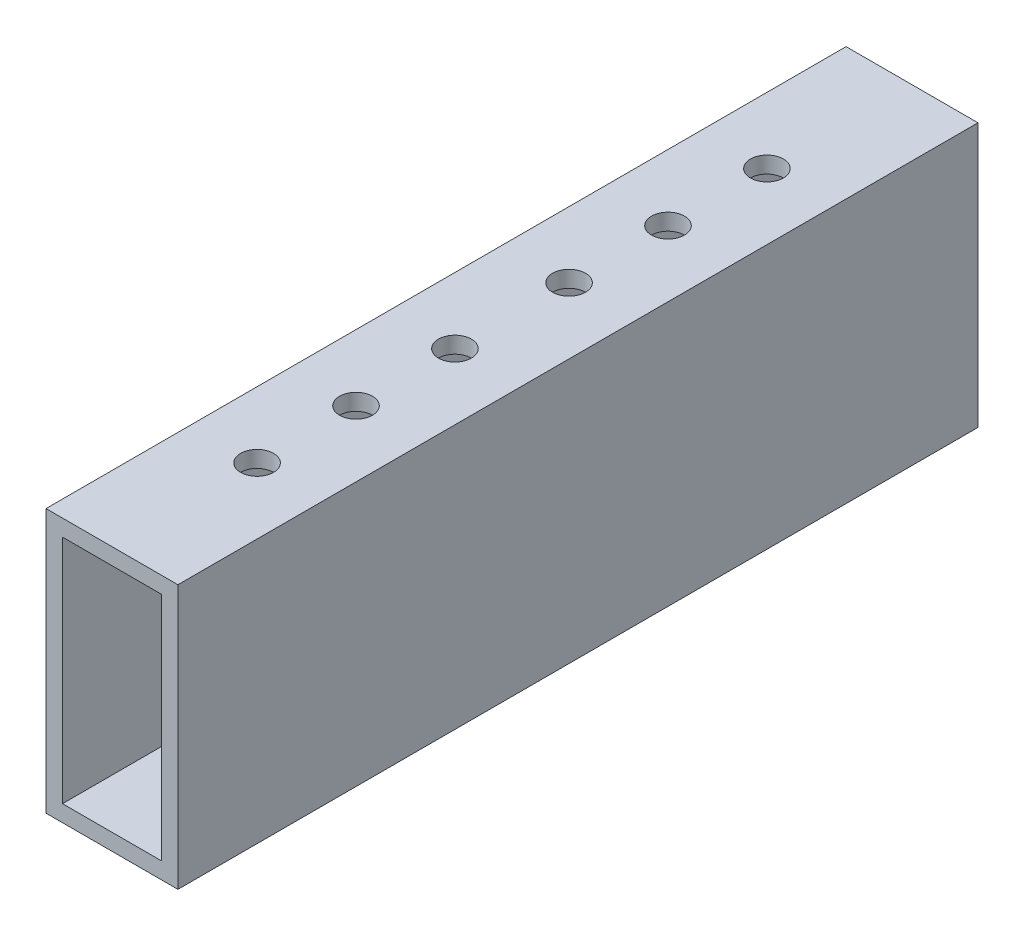
SolidWorks part; units mm, degrees
ref_plane "Front Plane" through (0, 0, 0) normal (0, 0, 1) x (1, 0, 0)
ref_plane "Top Plane" through (0, 0, 0) normal (0, 1, 0) x (1, 0, 0)
ref_plane "Right Plane" through (0, 0, 0) normal (1, 0, 0) x (0, 0, -1)
sketch "Sketch1" plane through (0, 0, 0) normal (0, 0, 1) x (1, 0, 0)
  line L0 (3.175, 47.625) -> (22.225, 47.625)
  line L1 (0, 0) -> (25.4, 0)
  line L2 (0, 0) -> (0, 50.8)
  line L3 (0, 50.8) -> (25.4, 50.8)
  line L4 (25.4, 0) -> (25.4, 50.8)
  line L5 (22.225, 3.175) -> (22.225, 47.625)
  line L6 (3.175, 3.175) -> (22.225, 3.175)
  line L7 (3.175, 3.175) -> (3.175, 47.625)
  dimension "D1" = 50.8
  dimension "D2" = 25.4
  dimension "D3" = 3.175
extrude "Boss-Extrude1" add sketch "Sketch1" along normal blind 154.051
sketch "Sketch2" plane through (0, 50.8, 0) normal (0, 1, 0) x (1, 0, 0)
  line L0 (25.4, -154.051) -> (0, -154.051) construction
  line L1 (0, -154.051) -> (0, 0) construction
  line L3 (0, -77.0255) -> (25.4, -77.0255) construction
  line L4 (25.4, -154.051) -> (25.4, 0) construction
  circle A0 centre (12.7, -126.111) radius 3.175
  circle A1 centre (12.7, -107.061) radius 3.175
  circle A2 centre (12.7, -88.011) radius 3.175
  circle A3 centre (12.7, -27.94) radius 3.175
  circle A4 centre (12.7, -46.99) radius 3.175
  circle A5 centre (12.7, -66.04) radius 3.175
  dimension "D3" = 6.35
  dimension "D4" = 6.35
  dimension "D5" = 6.35
  dimension "D1" = 19.05
  dimension "D2" = 19.05
  dimension "D6" = 27.94
  dimension "D7" = 12.7
  dimension "D8" = 12.7
  dimension "D9" = 12.7
extrude "Cut-Extrude1" cut sketch "Sketch2" against normal through all
